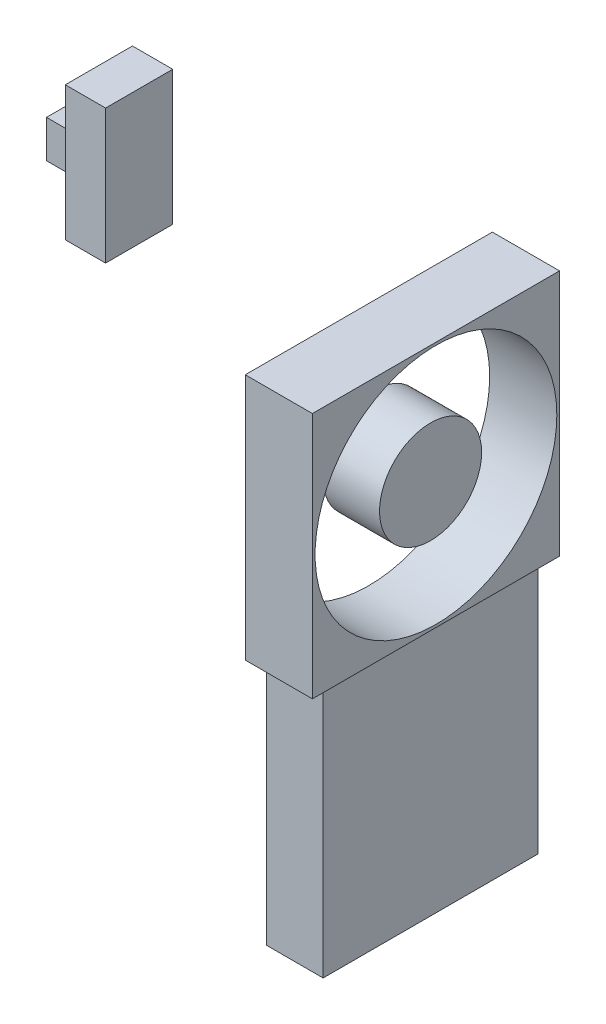
SolidWorks part; units mm, degrees
ref_plane "Front Plane" through (0, 0, 0) normal (0, 0, 1) x (1, 0, 0)
ref_plane "Top Plane" through (0, 0, 0) normal (0, 1, 0) x (1, 0, 0)
ref_plane "Right Plane" through (0, 0, 0) normal (1, 0, 0) x (0, 0, -1)
other "Configuration Table"
sketch "Sketch1" plane through (0, 0, 0) normal (1, 0, 0) x (0, 0, -1)
  line L1 (46, 94) -> (-46, 94)
  line L2 (46, 94) -> (46, 186)
  line L3 (46, 186) -> (-46, 186)
  line L4 (-46, 94) -> (-46, 186)
  line L5 (46, 94) -> (-46, 186) construction
  line L6 (46, 186) -> (-46, 94) construction
  point P0 (0, 140)
extrude "frame" add sketch "Sketch1" along normal blind 25 from offset 158 separate body
sketch "Sketch2" plane through (0, 0, 0) normal (1, 0, 0) x (0, 0, -1)
  circle A0 centre (0, 140) radius 45
extrude "bore" add sketch "Sketch2" along normal blind 27 from offset 157 separate body
combine bodies "Combine1" operation type subtract main body 102 bodies to subtract 103
sketch "Sketch3" plane through (0, 0, 0) normal (1, 0, 0) x (0, 0, -1)
  circle A0 centre (0, 140) radius 19
extrude "hub" add sketch "Sketch3" along normal blind 21 from offset 160 separate body
sketch "Sketch4" plane through (0, 0, 0) normal (1, 0, 0) x (0, 0, -1)
  line L0 (-46, 94) -> (46, 94) construction
  line L1 (40, 0) -> (-40, 0)
  line L2 (40, 0) -> (40, 94)
  line L3 (40, 94) -> (-40, 94)
  line L4 (-40, 0) -> (-40, 94)
  line L5 (40, 0) -> (-40, 94) construction
  line L6 (40, 94) -> (-40, 0) construction
  point P0 (0, 47)
extrude "fan_stand" add sketch "Sketch4" along normal blind 21 from offset 160 separate body
sketch "Sketch5" plane through (0, 0, 0) normal (1, 0, 0) x (0, 0, -1)
  line L1 (-25, 200) -> (-50, 200)
  line L2 (-25, 200) -> (-25, 250)
  line L3 (-25, 250) -> (-50, 250)
  line L4 (-50, 200) -> (-50, 250)
  line L5 (-25, 200) -> (-50, 250) construction
  line L6 (-25, 250) -> (-50, 200) construction
  point P0 (-37.5, 225)
extrude "blower_50mm" add sketch "Sketch5" along normal blind 15 from offset 95 separate body
sketch "Sketch6" plane through (0, 0, 0) normal (1, 0, 0) x (0, 0, -1)
  line L1 (-31, 214) -> (-42, 214)
  line L2 (-31, 214) -> (-31, 228)
  line L3 (-31, 228) -> (-42, 228)
  line L4 (-42, 214) -> (-42, 228)
  line L5 (-31, 214) -> (-42, 228) construction
  line L6 (-31, 228) -> (-42, 214) construction
  point P0 (-36.5, 221)
extrude "blower_nozzle" add sketch "Sketch6" along normal blind 15 from offset 80 separate body
